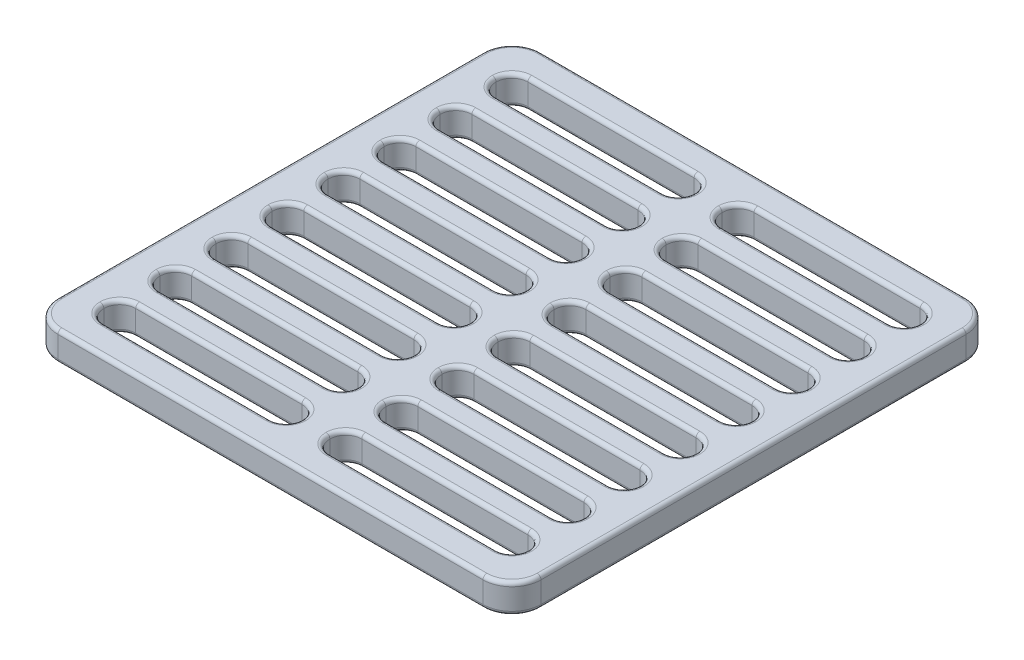
SolidWorks part; units mm, degrees
ref_plane "Front Plane" through (0, 0, 0) normal (0, 0, 1) x (1, 0, 0)
ref_plane "Top Plane" through (0, 0, 0) normal (0, 1, 0) x (1, 0, 0)
ref_plane "Right Plane" through (0, 0, 0) normal (1, 0, 0) x (0, 0, -1)
sketch "Sketch1" plane through (0, 0, 0) normal (0, 1, 0) x (1, 0, 0)
  line L1 (0, 0) -> (50, 0)
  line L2 (0, 0) -> (0, -50)
  line L3 (0, -50) -> (50, -50)
  line L4 (50, 0) -> (50, -50)
  dimension "D1" = 50
  dimension "D2" = 50
extrude "Boss-Extrude1" add sketch "Sketch1" along normal blind 3
sketch "Sketch4" plane through (0, 3, 0) normal (0, 1, 0) x (1, 0, 0)
  line L0 (0, 0) -> (0, -50) construction
  line L1 (3.05, -3.05) -> (23.55, -3.05)
  line L2 (3.05, -3.05) -> (3.05, -6.35)
  line L3 (3.05, -6.35) -> (23.55, -6.35)
  line L4 (23.55, -3.05) -> (23.55, -6.35)
  line L5 (50, 0) -> (0, 0) construction
  line L6 (26.45, -3.05) -> (26.45, -6.35)
  line L7 (26.45, -3.05) -> (46.95, -3.05)
  line L8 (46.95, -3.05) -> (46.95, -6.35)
  line L9 (26.45, -6.35) -> (46.95, -6.35)
  line L13 (3.05, -8.85) -> (3.05, -12.15)
  line L14 (3.05, -8.85) -> (23.55, -8.85)
  line L15 (23.55, -8.85) -> (23.55, -12.15)
  line L16 (3.05, -12.15) -> (23.55, -12.15)
  line L17 (26.45, -8.85) -> (26.45, -12.15)
  line L18 (26.45, -8.85) -> (46.95, -8.85)
  line L19 (46.95, -8.85) -> (46.95, -12.15)
  line L20 (26.45, -12.15) -> (46.95, -12.15)
  line L21 (3.05, -14.65) -> (3.05, -17.95)
  line L22 (3.05, -14.65) -> (23.55, -14.65)
  line L23 (23.55, -14.65) -> (23.55, -17.95)
  line L24 (3.05, -17.95) -> (23.55, -17.95)
  line L25 (26.45, -14.65) -> (26.45, -17.95)
  line L26 (26.45, -14.65) -> (46.95, -14.65)
  line L27 (46.95, -14.65) -> (46.95, -17.95)
  line L28 (26.45, -17.95) -> (46.95, -17.95)
  line L29 (3.05, -20.45) -> (3.05, -23.75)
  line L30 (3.05, -20.45) -> (23.55, -20.45)
  line L31 (23.55, -20.45) -> (23.55, -23.75)
  line L32 (3.05, -23.75) -> (23.55, -23.75)
  line L33 (26.45, -20.45) -> (26.45, -23.75)
  line L34 (26.45, -20.45) -> (46.95, -20.45)
  line L35 (46.95, -20.45) -> (46.95, -23.75)
  line L36 (26.45, -23.75) -> (46.95, -23.75)
  line L37 (3.05, -26.25) -> (3.05, -29.55)
  line L38 (3.05, -26.25) -> (23.55, -26.25)
  line L39 (23.55, -26.25) -> (23.55, -29.55)
  line L40 (3.05, -29.55) -> (23.55, -29.55)
  line L41 (26.45, -26.25) -> (26.45, -29.55)
  line L42 (26.45, -26.25) -> (46.95, -26.25)
  line L43 (46.95, -26.25) -> (46.95, -29.55)
  line L44 (26.45, -29.55) -> (46.95, -29.55)
  line L45 (3.05, -32.05) -> (3.05, -35.35)
  line L46 (3.05, -32.05) -> (23.55, -32.05)
  line L47 (23.55, -32.05) -> (23.55, -35.35)
  line L48 (3.05, -35.35) -> (23.55, -35.35)
  line L49 (26.45, -32.05) -> (26.45, -35.35)
  line L50 (26.45, -32.05) -> (46.95, -32.05)
  line L51 (46.95, -32.05) -> (46.95, -35.35)
  line L52 (26.45, -35.35) -> (46.95, -35.35)
  line L53 (3.05, -37.85) -> (3.05, -41.15)
  line L54 (3.05, -37.85) -> (23.55, -37.85)
  line L55 (23.55, -37.85) -> (23.55, -41.15)
  line L56 (3.05, -41.15) -> (23.55, -41.15)
  line L57 (26.45, -37.85) -> (26.45, -41.15)
  line L58 (26.45, -37.85) -> (46.95, -37.85)
  line L59 (46.95, -37.85) -> (46.95, -41.15)
  line L60 (26.45, -41.15) -> (46.95, -41.15)
  line L61 (3.05, -43.65) -> (3.05, -46.95)
  line L62 (3.05, -43.65) -> (23.55, -43.65)
  line L63 (23.55, -43.65) -> (23.55, -46.95)
  line L64 (3.05, -46.95) -> (23.55, -46.95)
  line L65 (26.45, -43.65) -> (26.45, -46.95)
  line L66 (26.45, -43.65) -> (46.95, -43.65)
  line L67 (46.95, -43.65) -> (46.95, -46.95)
  line L68 (26.45, -46.95) -> (46.95, -46.95)
  dimension "D1" = 3.05
  dimension "D2" = 3.05
  dimension "D3" = 3.3
  dimension "D6" = 8
  dimension "D4" = 20.5
  dimension "D5" = 2
extrude "Cut-Extrude2" cut sketch "Sketch4" against normal blind 3
fillet "Fillet3" radius 1.65 64 edges at (23.55, 1.5, 3.05) (23.55, 1.5, 6.35) (3.05, 1.5, 6.35) (23.55, 1.5, 41.15) (3.05, 1.5, 41.15) (3.05, 1.5, 37.85) (23.55, 1.5, 37.85) (46.95, 1.5, 35.35) (26.45, 1.5, 35.35) (26.45, 1.5, 32.05) (46.95, 1.5, 32.05) (23.55, 1.5, 35.35) (3.05, 1.5, 35.35) (3.05, 1.5, 32.05) (23.55, 1.5, 32.05) (46.95, 1.5, 29.55) (26.45, 1.5, 29.55) (26.45, 1.5, 26.25) (46.95, 1.5, 26.25) (46.95, 1.5, 46.95) (26.45, 1.5, 46.95) (26.45, 1.5, 43.65) (46.95, 1.5, 43.65) (23.55, 1.5, 46.95) (3.05, 1.5, 46.95) (3.05, 1.5, 43.65) (23.55, 1.5, 43.65) (46.95, 1.5, 41.15) (26.45, 1.5, 41.15) (26.45, 1.5, 37.85) (46.95, 1.5, 37.85) (23.55, 1.5, 17.95) (3.05, 1.5, 17.95) (3.05, 1.5, 14.65) (23.55, 1.5, 14.65) (46.95, 1.5, 12.15) (26.45, 1.5, 12.15) (26.45, 1.5, 8.85) (46.95, 1.5, 8.85) (23.55, 1.5, 12.15) (3.05, 1.5, 12.15) (3.05, 1.5, 8.85) (23.55, 1.5, 8.85) (46.95, 1.5, 6.35) (26.45, 1.5, 6.35) (26.45, 1.5, 3.05) (46.95, 1.5, 3.05) (23.55, 1.5, 29.55) (3.05, 1.5, 29.55) (3.05, 1.5, 26.25) (23.55, 1.5, 26.25) (46.95, 1.5, 23.75) (26.45, 1.5, 23.75) (26.45, 1.5, 20.45) (46.95, 1.5, 20.45) (23.55, 1.5, 23.75) (3.05, 1.5, 23.75) (3.05, 1.5, 20.45) (23.55, 1.5, 20.45) (46.95, 1.5, 17.95) (26.45, 1.5, 17.95) (26.45, 1.5, 14.65) (46.95, 1.5, 14.65) (3.05, 1.5, 3.05)
fillet "Fillet1" radius 3 4 edges at (0, 1.5, 0) (50, 1.5, 0) (50, 1.5, 50) (0, 1.5, 50)
fillet "Fillet2" radius 0.4 136 edges at (0.8787, 0, 49.1213) (25, 0, 50) (49.1213, 0, 49.1213) (50, 0, 25) (49.1213, 0, 0.8787) (25, 0, 0) (0.8787, 0, 0.8787) (0, 0, 25) (49.1213, 3, 0.8787) (50, 3, 25) (49.1213, 3, 49.1213) (25, 3, 50) (0.8787, 3, 49.1213) (0, 3, 25) (0.8787, 3, 0.8787) (25, 3, 0) (36.7, 0, 6.35) (36.7, 0, 3.05) (13.3, 0, 6.35) (13.3, 0, 3.05) (36.7, 3, 6.35) (36.7, 3, 3.05) (13.3, 3, 6.35) (13.3, 3, 3.05) (13.3, 0, 41.15) (13.3, 0, 37.85) (36.7, 0, 35.35) (36.7, 0, 32.05) (13.3, 0, 35.35) (13.3, 0, 32.05) (36.7, 0, 29.55) (36.7, 0, 26.25) (36.7, 0, 46.95) (36.7, 0, 43.65) (13.3, 0, 46.95) (13.3, 0, 43.65) (36.7, 0, 41.15) (36.7, 0, 37.85) (13.3, 0, 17.95) (13.3, 0, 14.65) (36.7, 0, 12.15) (36.7, 0, 8.85) (13.3, 0, 12.15) (13.3, 0, 8.85) (13.3, 0, 29.55) (13.3, 0, 26.25) (36.7, 0, 23.75) (36.7, 0, 20.45) (13.3, 0, 23.75) (13.3, 0, 20.45) (36.7, 0, 17.95) (36.7, 0, 14.65) (13.3, 3, 41.15) (13.3, 3, 37.85) (36.7, 3, 35.35) (36.7, 3, 32.05) (13.3, 3, 35.35) (13.3, 3, 32.05) (36.7, 3, 29.55) (36.7, 3, 26.25) (36.7, 3, 46.95) (36.7, 3, 43.65) (13.3, 3, 46.95) (13.3, 3, 43.65) (36.7, 3, 41.15) (36.7, 3, 37.85) (13.3, 3, 17.95) (13.3, 3, 14.65) (36.7, 3, 12.15) (36.7, 3, 8.85) (13.3, 3, 12.15) (13.3, 3, 8.85) (13.3, 3, 29.55) (13.3, 3, 26.25) (36.7, 3, 23.75) (36.7, 3, 20.45) (13.3, 3, 23.75) (13.3, 3, 20.45) (36.7, 3, 17.95) (36.7, 3, 14.65) (3.5333, 0, 5.8667) (3.5333, 0, 3.5333) (23.0667, 0, 3.5333) (23.0667, 0, 5.8667) (3.5333, 0, 40.6667) (3.5333, 0, 38.3333) (23.0667, 0, 38.3333) (23.0667, 0, 40.6667) (26.9333, 0, 34.8667) (26.9333, 0, 32.5333) (46.4667, 0, 32.5333) (46.4667, 0, 34.8667) (3.5333, 0, 34.8667) (3.5333, 0, 32.5333) (23.0667, 0, 32.5333) (23.0667, 0, 34.8667) (26.9333, 0, 29.0667) (26.9333, 0, 26.7333) (46.4667, 0, 26.7333) (46.4667, 0, 29.0667) (26.9333, 0, 46.4667) (26.9333, 0, 44.1333) (46.4667, 0, 44.1333) (46.4667, 0, 46.4667) (3.5333, 0, 46.4667) (3.5333, 0, 44.1333) (23.0667, 0, 44.1333) (23.0667, 0, 46.4667) (26.9333, 0, 40.6667) (26.9333, 0, 38.3333) (46.4667, 0, 38.3333) (46.4667, 0, 40.6667) (3.5333, 0, 17.4667) (3.5333, 0, 15.1333) (23.0667, 0, 15.1333) (23.0667, 0, 17.4667) (26.9333, 0, 11.6667) (26.9333, 0, 9.3333) (46.4667, 0, 9.3333) (46.4667, 0, 11.6667) (3.5333, 0, 11.6667) (3.5333, 0, 9.3333) (23.0667, 0, 9.3333) (23.0667, 0, 11.6667) (26.9333, 0, 5.8667) (26.9333, 0, 3.5333) (46.4667, 0, 3.5333) (46.4667, 0, 5.8667) (3.5333, 0, 29.0667) (3.5333, 0, 26.7333) (23.0667, 0, 26.7333) (23.0667, 0, 29.0667) (26.9333, 0, 23.2667) (26.9333, 0, 20.9333) (46.4667, 0, 20.9333) (46.4667, 0, 23.2667)
